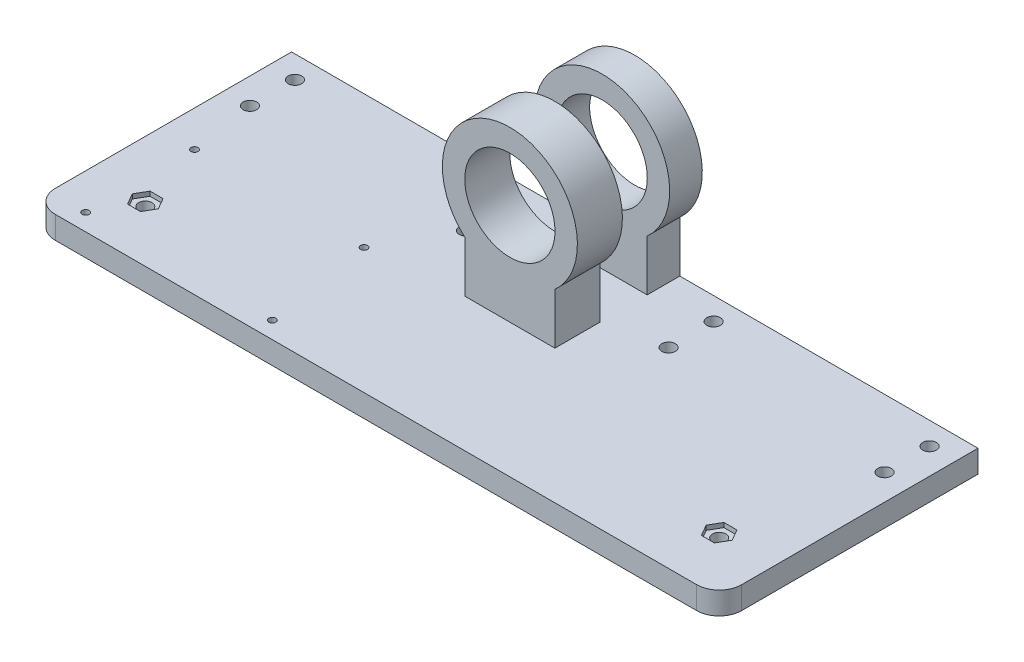
SolidWorks part; units mm, degrees
ref_plane "Front Plane" through (0, 0, 0) normal (0, 0, 1) x (1, 0, 0)
ref_plane "Top Plane" through (0, 0, 0) normal (0, 1, 0) x (1, 0, 0)
ref_plane "Right Plane" through (0, 0, 0) normal (1, 0, 0) x (0, 0, -1)
sketch "Sketch1" plane through (0, 0, 0) normal (0, 1, 0) x (1, 0, 0)
  line L0 (152.5, 115) -> (152.5, 0) construction
  line L1 (0, 0) -> (305, 0)
  line L2 (0, 0) -> (0, 115)
  line L3 (0, 115) -> (305, 115)
  line L4 (305, 0) -> (305, 115)
  line L5 (25, 90) -> (280, 90) construction
  line L6 (280, 25) -> (280, 90) construction
  line L7 (25, 25) -> (280, 25) construction
  line L8 (25, 25) -> (25, 90) construction
  line L9 (152.5, 57.5) -> (25, 57.5) construction
  line L10 (30.7735, 90) -> (27.8868, 95) construction
  line L11 (27.8868, 95) -> (22.1132, 95) construction
  line L12 (22.1132, 95) -> (19.2265, 90) construction
  line L13 (19.2265, 90) -> (22.1132, 85) construction
  line L14 (22.1132, 85) -> (27.8868, 85) construction
  line L15 (27.8868, 85) -> (30.7735, 90) construction
  line L16 (27.8868, 30) -> (30.7735, 25) construction
  line L17 (22.1132, 30) -> (27.8868, 30) construction
  line L18 (19.2265, 25) -> (22.1132, 30) construction
  line L19 (22.1132, 20) -> (19.2265, 25) construction
  line L20 (27.8868, 20) -> (22.1132, 20) construction
  line L21 (30.7735, 25) -> (27.8868, 20) construction
  line L22 (282.8868, 30) -> (277.1132, 30) construction
  line L23 (285.7735, 25) -> (282.8868, 30) construction
  line L24 (282.8868, 20) -> (285.7735, 25) construction
  line L25 (277.1132, 20) -> (282.8868, 20) construction
  line L26 (274.2265, 25) -> (277.1132, 20) construction
  line L27 (277.1132, 30) -> (274.2265, 25) construction
  line L28 (277.1132, 85) -> (274.2265, 90) construction
  line L29 (282.8868, 85) -> (277.1132, 85) construction
  line L30 (285.7735, 90) -> (282.8868, 85) construction
  line L31 (282.8868, 95) -> (285.7735, 90) construction
  line L32 (277.1132, 95) -> (282.8868, 95) construction
  line L33 (274.2265, 90) -> (277.1132, 95) construction
  line L34 (107.5, 105) -> (107.5, 115) construction
  line L35 (132.5, 0) -> (172.5, 0) construction
  line L37 (132.5, 115) -> (172.5, 115) construction
  line L41 (132.5, 25) -> (172.5, 25) construction
  line L50 (305, 14.5) -> (253.3, 14.5) construction
  line L51 (30.7735, 90) -> (22.1132, 95) construction
  line L54 (0, 115) -> (90.0836, 115) construction
  line L55 (0, 115) -> (0, 84.5) construction
  line L62 (0, 84.5) -> (0, 69.5) construction
  line L64 (62, 0) -> (62, 115) construction
  line L65 (253.3, 14.5) -> (253.3, 0) construction
  line L67 (253.3, 14.5) -> (280.2, 14.5) construction
  circle A1 centre (25, 90) radius 5 construction
  circle A3 centre (280, 25) radius 3
  circle A4 centre (25, 25) radius 3
  circle A18 centre (107.5, 105) radius 3
  circle A20 centre (107.5, 85) radius 3
  circle A23 centre (197.5, 105) radius 3
  circle A24 centre (197.5, 85) radius 3
  circle A27 centre (107.5, 65) radius 3 [skipped]
  circle A28 centre (107.5, 45) radius 3 [skipped]
  circle A29 centre (11.5, 85) radius 3
  circle A30 centre (11.5, 105) radius 3
  circle A31 centre (293.5, 105) radius 3
  circle A32 centre (293.5, 85) radius 3
  dimension "D3" = 6
  dimension "D1" = 305
  dimension "D2" = 115
  dimension "D5" = 10
  dimension "D6" = 40
  dimension "D15" = 62
  dimension "D18" = 51.7
  dimension "D19" = 14.5
  dimension "D20" = 26.9
  dimension "D8" = 20
  dimension "D9" = 45
  dimension "D11" = 11.5
  dimension "D4" = 25
  dimension "D14" = 2
  dimension "D7" = 4
  dimension "D10" = 2
extrude "Boss-Extrude1" add sketch "Sketch1" along normal blind 10
sketch "Sketch7" plane through (0, 10, 0) normal (0, 1, 0) x (1, 0, 0)
  line L0 (0, 0) -> (305, 0) construction
  line L1 (132.5, 59.5) -> (172.5, 59.5)
  line L2 (132.5, 59.5) -> (132.5, 79.5)
  line L3 (132.5, 79.5) -> (172.5, 79.5)
  line L4 (172.5, 59.5) -> (172.5, 79.5)
  line L5 (152.5, 0) -> (152.5, 115) construction
  line L6 (305, 115) -> (0, 115) construction
  line L18 (132.5, 100.5) -> (172.5, 100.5)
  line L19 (132.5, 100.5) -> (132.5, 115)
  line L20 (132.5, 115) -> (172.5, 115)
  line L21 (172.5, 100.5) -> (172.5, 115)
  point P11 (152.5, 79.5)
  point P20 (152.5, 100.5)
  dimension "D1" = 40
  dimension "D2" = 20
  dimension "D4" = 14.5
  dimension "D3" = 21
extrude "Boss-Extrude2" add sketch "Sketch7" along normal blind 22.6393
sketch "Sketch11" plane through (0, 0, -59.5) normal (0, 0, 1) x (1, 0, 0)
  circle A0 centre (152.5, 55) radius 30
  circle A1 centre (152.5, 55) radius 20.05
  dimension "D1" = 60
  dimension "D2" = 40.1
extrude "Boss-Extrude3" add sketch "Sketch11" against normal up to surface (55.5 mm away) up to face at (152.5, 13.1598, -115)
ref_plane "Plane1" through (0, 0, -57.5) normal (0, 0, 1) x (1, 0, 0)
sketch "Sketch12" plane through (305, 0, 0) normal (1, 0, 0) x (0, 0, -1)
  line L0 (115, 85) -> (59.5, 85) construction
  line L1 (79.5, 10) -> (100.5, 10)
  line L2 (79.5, 10) -> (79.5, 85)
  line L3 (79.5, 85) -> (100.5, 85)
  line L4 (100.5, 10) -> (100.5, 85)
  line L6 (100.5, 32.6393) -> (100.5, 10) construction
extrude "Cut-Extrude2" cut sketch "Sketch12" against normal through all
sketch "Sketch6" plane through (0, 10, 0) normal (0, 1, 0) x (1, 0, 0)
  line L0 (152.5, 115) -> (152.5, 0) construction
  line L8 (0, 0) -> (305, 0) construction
  line L9 (152.5, 57.5) -> (0, 57.5) construction
  line L10 (0, 115) -> (0, 0) construction
  line L29 (27.8868, 30) -> (30.7735, 25)
  line L30 (274.2265, 25) -> (277.1132, 20)
  line L31 (277.1132, 20) -> (282.8868, 20)
  line L32 (282.8868, 20) -> (285.7735, 25)
  line L33 (285.7735, 25) -> (282.8868, 30)
  line L34 (282.8868, 30) -> (277.1132, 30)
  line L35 (277.1132, 30) -> (274.2265, 25)
  line L36 (22.1132, 30) -> (27.8868, 30)
  line L37 (19.2265, 25) -> (22.1132, 30)
  line L38 (22.1132, 20) -> (19.2265, 25)
  line L39 (27.8868, 20) -> (22.1132, 20)
  line L40 (30.7735, 25) -> (27.8868, 20)
  circle A0 centre (280, 25) radius 5 construction
  dimension "D1" = 10
extrude "Cut-Extrude1" cut sketch "Sketch6" against normal blind 2
sketch "Sketch16" plane through (0, 10, 0) normal (0, 1, 0) x (1, 0, 0)
  line L0 (0, 0) -> (305, 0) construction
  line L1 (0, 115) -> (0, 0) construction
  circle A0 centre (16, 7.5) radius 1.55
  circle A1 centre (98.95, 7.5) radius 1.55
  circle A2 centre (16, 55.866) radius 1.55
  circle A3 centre (91.33, 55.866) radius 1.55
  dimension "D1" = 3.1
  dimension "D2" = 7.5
  dimension "D3" = 82.95
  dimension "D4" = 16
  dimension "D5" = 48.366
  dimension "D6" = 75.33
extrude "Cut-Extrude3" cut sketch "Sketch16" against normal through all
fillet "Fillet3" radius 10 2 edges at (305, 5, 0) (0, 5, 0)
chamfer "Chamfer2" distance 1.65 4 edges at (98.95, 0, -5.95) (91.33, 0, -54.316) (16, 0, -5.95) (16, 0, -54.316)
equation "\"joint_width\"=4"
equation "\"short_base_length\"=11.5"
equation "\"D2@Sketch1\"=\"short_base_length\""
equation "\"outer_diam_main_joint\"=6"
equation "\"D1@Sketch11\"=\"outer_diam_main_joint\""
equation "\"D1@Sketch7\"=\"outer_diam_main_joint\"-2"
equation "\"D1@Boss-Extrude2\"=(\"outer_diam_main_joint\"/2)+1.5cm-sqr((\"outer_diam_main_joint\"/2)^2-((\"outer_diam_main_joint\"-2)/2)^2)"
equation "\"D6@Sketch1\"=\"outer_diam_main_joint\"-2"
equation "\"pulleyside\"=1.5"
